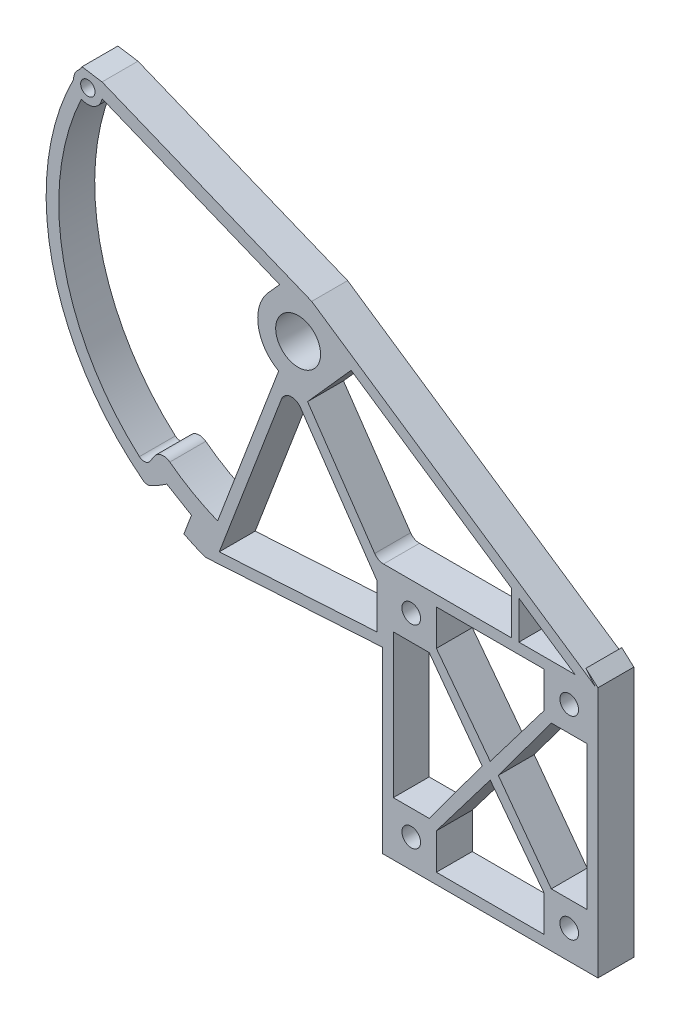
SolidWorks part; units mm, degrees
material "Magnesium Alloy"
ref_plane "Front Plane" through (0, 0, 0) normal (0, 0, 1) x (1, 0, 0)
ref_plane "Top Plane" through (0, 0, 0) normal (0, 1, 0) x (1, 0, 0)
ref_plane "Right Plane" through (0, 0, 0) normal (1, 0, 0) x (0, 0, -1)
sketch "Sketch1" plane through (0, 0, 0) normal (0, 0, 1) x (1, 0, 0)
  line L3 (22.6053, 67.0523) -> (98.8053, 67.0523)
  line L4 (98.8053, 155.9523) -> (98.8053, 67.0523)
  line L7 (60.7053, 155.2939) -> (60.7053, 67.0523) construction
  line L8 (184.9087, 111.5023) -> (-17.2677, 111.5023) construction
  line L11 (98.8053, 155.9523) -> (-49.1612, 287.7)
  line L14 (22.6053, 67.0523) -> (22.6053, 130.2741)
  line L15 (-40.152, 126.5029) -> (22.6053, 130.2741)
  arc A1 (-40.152, 126.5029) -> (-49.1612, 287.7) centre (-7.475, 209.1795) cw
  dimension "D3" = 88.9
  dimension "D1" = 88.9
  dimension "D7" = 44.45
  dimension "D8" = 38.1
  dimension "D9" = 76.2
extrude "Boss-Extrude1" add sketch "Sketch1" along normal blind 12.7
sketch "Sketch2" plane through (0, 0, 12.7) normal (0, 0, 1) x (1, 0, 0)
  line L2 (22.6053, 67.0523) -> (98.8053, 67.0523) construction
  line L3 (22.6053, 130.2741) -> (22.6053, 67.0523) construction
  circle A0 centre (-7.2397, 209.0383) radius 7.9375
  dimension "D2" = 15.875
  dimension "D1" = 141.986
  dimension "D3" = 29.845
extrude "Cut-Extrude1" cut sketch "Sketch2" against normal blind 25.4
ref_axis "Axis1" through (-7.2397, 209.0383, 0) along (0, 0, 1)
ref_axis "Axis2" through (-7.475, 209.1795, 12.7) along (0, 0, -1)
sketch "Sketch3" plane through (0, 0, 12.7) normal (0, 0, 1) x (1, 0, 0)
  line L0 (41.6553, 70.8623) -> (41.6553, 83.5623)
  line L1 (41.6553, 83.5623) -> (60.7053, 108.6448)
  line L2 (60.7053, 108.6448) -> (79.7553, 83.5623)
  line L3 (79.7553, 83.5623) -> (79.7553, 70.8623)
  line L4 (79.7553, 70.8623) -> (41.6553, 70.8623)
  line L5 (26.4153, 86.1023) -> (39.1153, 86.1023)
  line L6 (39.1153, 86.1023) -> (57.8478, 111.5023)
  line L7 (57.8478, 111.5023) -> (39.1153, 136.9023)
  line L8 (39.1153, 136.9023) -> (26.4153, 136.9023)
  line L9 (26.4153, 136.9023) -> (26.4153, 86.1023)
  line L10 (94.9953, 86.1023) -> (82.2953, 86.1023)
  line L11 (82.2953, 86.1023) -> (63.5628, 111.5023)
  line L12 (63.5628, 111.5023) -> (82.2953, 136.9023)
  line L13 (82.2953, 136.9023) -> (94.9953, 136.9023)
  line L14 (94.9953, 136.9023) -> (94.9953, 86.1023)
  line L15 (41.6553, 152.1423) -> (41.6553, 139.4423)
  line L16 (41.6553, 139.4423) -> (60.7053, 114.3598)
  line L17 (60.7053, 114.3598) -> (79.7553, 139.4423)
  line L18 (79.7553, 139.4423) -> (79.7553, 152.1423)
  line L19 (79.7553, 152.1423) -> (41.6553, 152.1423)
  line L20 (22.6053, 67.0523) -> (98.8053, 67.0523) construction
  line L21 (98.8053, 67.0523) -> (98.8053, 155.9523) construction
  line L22 (22.6053, 130.2741) -> (22.6053, 67.0523) construction
  dimension "D1" = 3.81
  dimension "D2" = 3.81
  dimension "D3" = 3.81
  dimension "D4" = 3.81
  dimension "D5" = 19.05
  dimension "D6" = 19.05
  dimension "D7" = 19.05
  dimension "D8" = 19.05
  dimension "D10" = 19.05
  dimension "D11" = 12.7
  dimension "D12" = 12.7
  dimension "D13" = 12.7
  dimension "D14" = 12.7
  dimension "D16" = 5.715
  dimension "D17" = 5.715
extrude "Cut-Extrude2" cut sketch "Sketch3" against normal blind 15.24
sketch "Sketch5" plane through (0, 0, 12.7) normal (0, 0, 1) x (1, 0, 0)
  line L2 (-0.7594, 237.8017) -> (-42.8182, 275.2504)
  line L3 (98.8053, 155.9523) -> (-49.1612, 287.7) construction
  line L5 (-17.9104, 218.5393) -> (-0.7594, 237.8017)
  line L6 (-5.268, 223.1891) -> (3.9831, 233.579)
  line L7 (3.9831, 233.579) -> (15.3651, 223.4446)
  line L8 (15.3651, 223.4446) -> (6.3804, 213.3538)
  line L11 (79.7553, 152.1423) -> (41.6553, 152.1423) construction
  line L12 (-35.7205, 139.7771) -> (-14.1244, 196.5189)
  line L14 (20.7003, 149.6023) -> (-10.5461, 195.2095)
  line L15 (-10.5461, 195.2095) -> (-35.1284, 130.6216)
  line L17 (26.4153, 136.9023) -> (26.4153, 86.1023) construction
  line L18 (-35.1284, 130.6216) -> (20.7003, 133.9765)
  line L19 (20.7003, 133.9765) -> (20.7003, 149.6023)
  line L20 (-40.152, 126.5029) -> (22.6053, 130.2741) construction
  arc A0 (-35.7205, 139.7771) -> (-42.8182, 275.2504) centre (-7.475, 209.1795) cw
  arc A1 (-49.1612, 287.7) -> (-40.152, 126.5029) centre (-7.475, 209.1795) ccw construction
  arc A2 (-14.1244, 196.5189) -> (-17.9104, 218.5393) centre (-7.2397, 209.0383) cw
  circle A3 centre (-7.2397, 209.0383) radius 7.9375 construction
  arc A4 (-5.268, 223.1891) -> (6.3804, 213.3538) centre (-7.2397, 209.0383) cw
  dimension "D1" = 13.97
  dimension "D4" = 6.35
  dimension "D6" = 6.35
  dimension "D2" = 5.08
  dimension "D5" = 6.35
  dimension "D7" = 15.24
  dimension "D8" = 5.08
  dimension "D9" = 3.81
  dimension "D10" = 13.97
  dimension "D11" = 2.54
  dimension "D12" = 5.715
  dimension "D13" = 3.81
extrude "Cut-Extrude4" cut sketch "Sketch5" against normal blind 12.7 contours A2 L5 L2 A0 | L15 L18 L19 L14 | L12 A2 L5 L2 A0 | L8 A4 L6 L7 region at (-46.1903, 210.5429, 12.7)
sketch "Sketch4" plane through (0, 0, 12.7) normal (0, 0, 1) x (1, 0, 0)
  line L3 (20.9682, 155.9523) -> (-3.9035, 192.2549)
  line L4 (-3.9035, 192.2549) -> (20.9522, 220.1704)
  line L15 (20.7003, 149.6023) -> (-10.5461, 195.2095) construction
  line L16 (15.3651, 223.4446) -> (6.3804, 213.3538) construction
  line L18 (91.166, 155.9523) -> (70.846, 155.9523)
  line L19 (70.846, 155.9523) -> (70.846, 174.045)
  line L20 (70.846, 174.045) -> (91.166, 155.9523)
  line L21 (98.8053, 155.9523) -> (-49.1612, 287.7) construction
  line L22 (79.7553, 152.1423) -> (41.6553, 152.1423) construction
  line L23 (68.306, 155.9523) -> (68.306, 178.007)
  line L24 (68.306, 178.007) -> (20.9522, 220.1704)
  line L26 (20.9682, 155.9523) -> (68.306, 155.9523)
  dimension "D1" = 3.81
  dimension "D2" = 5.08
  dimension "D3" = 20.32
  dimension "D4" = 3.81
  dimension "D5" = 2.54
  dimension "D6" = 6.35
  dimension "D8" = 3.81
extrude "Cut-Extrude3" cut sketch "Sketch4" against normal blind 12.7
sketch "Sketch6" plane through (0, 0, 12.7) normal (0, 0, 1) x (1, 0, 0)
  line L0 (-45.205, 275.6751) -> (-52.1749, 281.881)
  line L1 (-56.3239, 139.1982) -> (-53.0517, 147.7956)
  line L3 (98.8053, 155.9523) -> (-49.1612, 287.7) construction
  line L4 (-35.7205, 139.7771) -> (-14.1244, 196.5189) construction
  arc A0 (-45.205, 275.6751) -> (-53.0517, 147.7956) centre (-7.475, 209.1795) ccw
  arc A1 (-52.1749, 281.881) -> (-56.3239, 139.1982) centre (-7.475, 209.1795) ccw
  dimension "D1" = 8.89
  dimension "D2" = 76.454
  dimension "D3" = 6.35
  dimension "D4" = 19.05
extrude "Cut-Extrude5" [suppressed] cut sketch "Sketch6" against normal blind 3.81
fillet "Fillet4" radius 3.81 2 edges at (-10.5461, 195.2095, 6.35) (20.9682, 155.9523, 6.35)
sketch "Sketch10" plane through (0, 0, 12.7) normal (0, 0, 1) x (1, 0, 0)
  line L0 (22.6053, 67.0523) -> (98.8053, 67.0523) construction
  line L1 (98.8053, 67.0523) -> (98.8053, 155.9523) construction
  line L2 (22.6053, 130.2741) -> (22.6053, 67.0523) construction
  circle A0 centre (32.7653, 77.2123) radius 3.302
  circle A1 centre (32.7653, 145.7923) radius 3.302
  circle A2 centre (88.6453, 145.7923) radius 3.302
  circle A3 centre (88.6453, 77.2123) radius 3.302
  dimension "D1" = 6.604
  dimension "D2" = 10.16
  dimension "D3" = 10.16
  dimension "D4" = 10.16
  dimension "D5" = 10.16
extrude "Cut-Extrude8" cut sketch "Sketch10" against normal up to next
sketch "Sketch11" plane through (0, 0, 12.7) normal (0, 0, 1) x (1, 0, 0)
  line L0 (-53.7, 142.0991) -> (-44.9647, 136.9105)
  line L1 (-44.9647, 136.9105) -> (-50.0205, 123.6268)
  line L2 (-50.0205, 123.6268) -> (-66.8677, 134.9879)
  line L5 (-35.7205, 139.7771) -> (-14.1244, 196.5189) construction
  arc A0 (-42.8182, 275.2504) -> (-35.7205, 139.7771) centre (-7.475, 209.1795) ccw construction
  arc A3 (-53.7, 142.0991) -> (-60.8297, 138.0705) centre (-77.91, 176.623) cw
  arc A4 (-49.1612, 287.7) -> (-40.152, 126.5029) centre (-7.475, 209.1795) ccw construction
  arc A5 (-60.8297, 138.0705) -> (-66.8677, 134.9879) centre (-44.9891, 99.5886) ccw
  dimension "D1" = 10.16
  dimension "D2" = 81.28
  dimension "D3" = 7.62
  dimension "D4" = 20.32
  dimension "D5" = 15.24
extrude "Cut-Extrude9" cut sketch "Sketch11" against normal blind 12.7
fillet "Fillet6" [suppressed] radius 3.81
sketch "Sketch13" plane through (0, 0, 12.7) normal (0, 0, 1) x (1, 0, 0)
  line L0 (98.8053, 155.9523) -> (-49.1612, 287.7) construction
  line L1 (-50.3104, 281.9213) -> (-42.8182, 275.2504)
  line L2 (-42.8182, 275.2504) -> (-55.8246, 151.936)
  line L3 (-55.8246, 151.936) -> (-61.138, 143.7544)
  arc A0 (-50.3104, 281.9213) -> (-61.138, 143.7544) centre (-7.2397, 209.0383) ccw
  arc A1 (-42.8182, 275.2504) -> (-35.7205, 139.7771) centre (-7.475, 209.1795) ccw construction
  arc A2 (-42.8182, 275.2504) -> (-35.7205, 139.7771) centre (-7.475, 209.1795) ccw construction
  dimension "D3" = 84.6582
  dimension "D1" = 5.08
  dimension "D2" = 7.62
  dimension "D4" = 23.495
extrude "Cut-Extrude10" cut sketch "Sketch13" against normal blind 15.24
fillet "Fillet8" radius 2.54 2 edges at (-60.8297, 138.0705, 6.35) (-61.138, 143.7544, 6.35)
fillet "Fillet9" radius 3.81 1 edges at (-55.8246, 151.936, 6.35)
sketch "Sketch14" plane through (0, 0, 12.7) normal (0, 0, 1) x (1, 0, 0)
  line L0 (-0.7594, 237.8017) -> (-90.2849, 256.2973)
  line L1 (-90.2849, 256.2973) -> (-56.5034, 294.2374)
  line L2 (-56.5034, 294.2374) -> (2.6187, 241.5957)
  line L3 (2.6187, 241.5957) -> (-0.7594, 237.8017)
  line L4 (98.8053, 155.9523) -> (-49.1612, 287.7) construction
  dimension "D1" = 50.8
extrude "Cut-Extrude11" cut sketch "Sketch14" against normal blind 12.7
sketch "Sketch15" plane through (0, 0, 12.7) normal (0, 0, 1) x (1, 0, 0)
  line L0 (2.6187, 241.5957) -> (-83.6954, 254.9359)
  line L1 (-83.6954, 254.9359) -> (-84.4714, 249.9156)
  line L2 (-84.4714, 249.9156) -> (-1.4045, 237.0772)
  line L3 (-17.9104, 218.5393) -> (2.6187, 241.5957) construction
  line L4 (-1.4045, 237.0772) -> (2.6187, 241.5957)
  dimension "D1" = 5.08
extrude "Boss-Extrude2" add sketch "Sketch15" against normal blind 12.7
sketch "Sketch16" plane through (0, 0, 12.7) normal (0, 0, 1) x (1, 0, 0)
  circle A0 centre (-81.6167, 249.4744) radius 5.08
  circle A1 centre (-81.6167, 249.4744) radius 2.54
  dimension "D1" = 10.16
extrude "Boss-Extrude3" add sketch "Sketch16" against normal blind 12.7
sketch "Sketch17" plane through (0, 0, 12.7) normal (0, 0, 1) x (1, 0, 0)
  circle A0 centre (-81.6167, 249.4744) radius 2.54
extrude "Cut-Extrude12" cut sketch "Sketch17" against normal blind 12.7
sketch "Sketch18" plane through (0, 0, 12.7) normal (0, 0, 1) x (1, 0, 0)
  line L0 (-76.5963, 248.6984) -> (1.9776, 219.9549)
  line L1 (1.9776, 219.9549) -> (91.166, 155.9523)
  line L2 (91.166, 155.9523) -> (97.7253, 155.9523)
  line L3 (97.7253, 155.9523) -> (11.1826, 258.9905)
  line L4 (11.1826, 258.9905) -> (-76.5963, 256.9042)
  line L5 (-76.5963, 256.9042) -> (-76.5963, 248.6984)
  arc A0 (6.3804, 213.3538) -> (-5.268, 223.1891) centre (-7.2397, 209.0383) ccw construction
  point P12 (90.5883, 155.9523)
  point P13 (89.7397, 157.2223)
extrude "Cut-Extrude13" cut sketch "Sketch18" against normal blind 12.7
ref_plane "Plane1" through (97.7253, 155.9523, 12.7) normal (1, 0, 0) x (0, 0, -1)
sketch "Sketch20" plane through (0, 0, 12.7) normal (0, 0, 1) x (1, 0, 0)
  line L0 (90.7453, 155.9523) -> (-0.8897, 217.9283)
  line L1 (70.846, 155.9523) -> (97.7253, 155.9523) construction
  line L2 (-0.8897, 217.9283) -> (-76.5963, 248.6984)
  line L3 (-76.5963, 248.6984) -> (-76.5963, 253.8387)
  line L4 (-76.5963, 253.8387) -> (-2.4442, 223.7004)
  line L5 (-2.4442, 223.7004) -> (97.7253, 155.9523)
  line L6 (97.7253, 150.48) -> (97.7253, 161.4246) construction
  line L7 (97.7253, 155.9523) -> (90.7453, 155.9523)
  point P13 (-0.6129, 217.238)
  point P14 (0.1942, 222.5573)
  dimension "D1" = 6.35
  dimension "D2" = 8.89
extrude "Boss-Extrude4" add sketch "Sketch20" against normal blind 12.7
